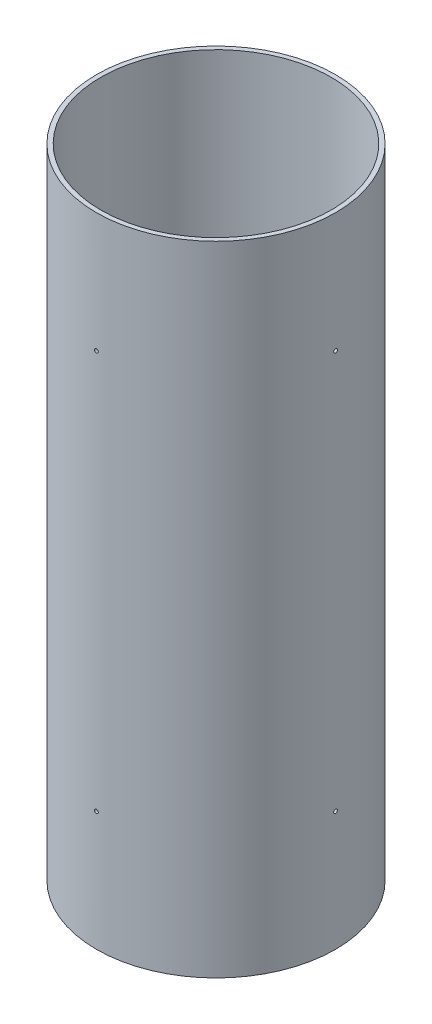
SolidWorks part; units mm, degrees
material "E-Glass Fiber"
ref_plane "Front Plane" through (0, 0, 0) normal (0, 0, 1) x (1, 0, 0)
ref_plane "Top Plane" through (0, 0, 0) normal (0, 1, 0) x (1, 0, 0)
ref_plane "Right Plane" through (0, 0, 0) normal (1, 0, 0) x (0, 0, -1)
sketch "Coupler Profile" plane through (0, 0, 0) normal (0, 1, 0) x (1, 0, 0)
  circle A0 centre (0, 0) radius 73.3425
  circle A1 centre (0, 0) radius 76.1746
  dimension "D1" = 146.685
  dimension "D2" = 152.3492
extrude "Coupler Body" add sketch "Coupler Profile" along normal blind 406.4
sketch "Sketch1" plane through (0, 0, 0) normal (0, 0, 1) x (1, 0, 0)
  line L0 (76.1746, 406.4) -> (-76.1746, 406.4) construction
  circle A0 centre (0, 76.2) radius 1.1906
  circle A1 centre (0, 330.2) radius 1.1906
  point P4 (0, 0)
  dimension "D3" = 2.3813
  dimension "D1" = 76.2
  dimension "D2" = 76.2
extrude "Cut-Extrude1" cut sketch "Sketch1" against normal through all both and the other way through all
pattern_circular "CirPattern1" count 4 over 360 about axis through (0, 0, 0) along (0, 1, 0) of "Cut-Extrude1"
equation "\"Length\"=16"
equation "\"Outer Diameter\"= 5.998"
equation "\"Inner Diameter\"= 5.775"
equation "\"Wall Thickness\"= 0.111"
equation "\"D1@Coupler Profile\" = \"Inner Diameter\""
equation "\"D2@Coupler Profile\" = \"Outer Diameter\""
equation "\"D1@Coupler Body\" = \"Length\""
equation "\"Shear Pin Dia\"= 3 / 32"
equation "\"Shear Pin Offset\"= 3"
equation "\"D1@Sketch1\"=\"Shear Pin Offset\""
equation "\"D2@Sketch1\"=\"Shear Pin Offset\""
equation "\"D3@Sketch1\"=\"Shear Pin Dia\""
